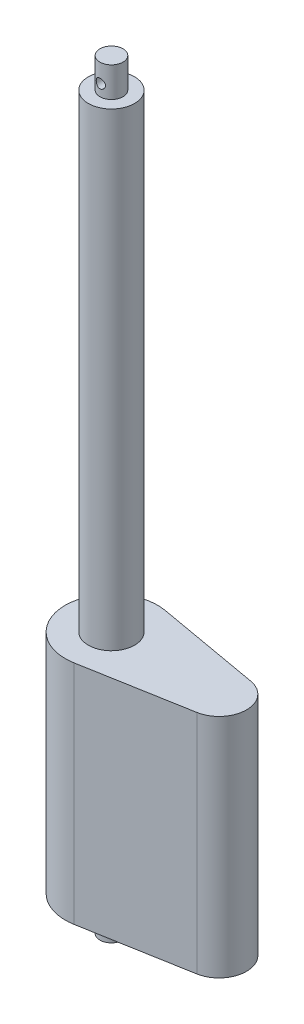
SolidWorks part; units mm, degrees
ref_plane "Front" through (0, 0, 0) normal (0, 0, 1) x (1, 0, 0)
ref_plane "Top" through (0, 0, 0) normal (0, 1, 0) x (1, 0, 0)
ref_plane "Right" through (0, 0, 0) normal (1, 0, 0) x (0, 0, -1)
sketch "Sketch7" plane through (0, 0, 0) normal (1, 0, 0) x (0, 0, -1)
  line L1 (-20, 7) -> (-20, 105)
  line L4 (-10, 308) -> (-5, 308)
  line L5 (-5, 308) -> (-5, 321)
  line L6 (-5, 321) -> (0, 321)
  line L7 (0, 321) -> (0, -8)
  line L9 (-5, -8) -> (0, -8)
  line L10 (-10, 308) -> (-10, 105)
  line L11 (-10, 105) -> (-20, 105)
  line L12 (-5, -8) -> (-5, 7)
  line L13 (-5, 7) -> (-20, 7)
  point P5 (-20, 1.0114)
  point P10 (-29.2194, 0)
  point P11 (0, 0)
  point P12 (0, 313)
  point P13 (0, 320)
  point P16 (0, 0)
  point P17 (0, 0)
  dimension "D1" = 8
  dimension "D2" = 8
  dimension "D3" = 98
  dimension "D5" = 12
  dimension "D7" = 10
  dimension "D8" = 20
  dimension "D11" = 5
  dimension "D9" = 15
  dimension "D10" = 5
  dimension "D4" = 1
  dimension "D6" = 320
revolve "Revolve2" add sketch "Sketch7" angle 360 about L7
sketch "Sketch8" plane through (0, 0, 0) normal (0, 0, 1) x (1, 0, 0)
  line L0 (-5, -8) -> (5, -8) construction
  line L2 (0, 321) -> (0, 313) construction
  line L3 (5, 321) -> (-5, 321) construction
  line L4 (-5, -8) -> (5, -8) construction
  line L5 (0, -8) -> (0, 0) construction
  circle A1 centre (0, 313) radius 2
  circle A2 centre (0, 0) radius 2
  dimension "D2" = 8
  dimension "D1" = 4
  dimension "D4" = 4
  dimension "D3" = 8
extrude "Cut-Extrude2" cut sketch "Sketch8" against normal through all and the other way through all
sketch "Sketch10" plane through (0, 105, 0) normal (0, 1, 0) x (1, 0, 0)
  line L0 (0, 0) -> (46.5567, 0) construction
  line L1 (3.491, 19.693) -> (48.6292, 11.6912)
  line L2 (48.6292, -11.6912) -> (3.491, -19.693)
  circle A1 centre (0, 0) radius 20 construction
  arc A2 (48.6292, 11.6912) -> (48.6292, -11.6912) centre (46.5567, 0) cw
  arc A3 (3.491, 19.693) -> (3.491, -19.693) centre (0, 0) ccw
  point P9 (48.6292, 0)
extrude "Boss-Extrude4" add sketch "Sketch10" against normal up to surface (98 mm away) up to face at (0, 7, 5)
sketch "Sketch11" plane through (0, 0, 0) normal (0, 0, 1) x (1, 0, 0)
  line L0 (0, 313) -> (0, 0)
  point P3 (0, 330)
  point P4 (0, 0)
equation "\"mountingHoleDistance\"=8"
equation "\"actuatorLength\" = 1"
equation "\"D1@Sketch7\"= \"mountingHoleDistance\""
equation "\"D2@Sketch7\"=\"mountingHoleDistance\""
equation "\"MotorHousingHeight\" = 98"
equation "\"D3@Sketch7\"=\"MotorHousingHeight\""
equation "\"acutatorMinimumLength\" = 320"
equation "\"D3@Sketch8\"=\"mountingHoleDistance\""
equation "\"D2@Sketch8\"=\"mountingHoleDistance\""
equation "\"D4@Sketch7\"=\"actuatorLength\""
equation "\"D6@Sketch7\"=\"acutatorMinimumLength\""
